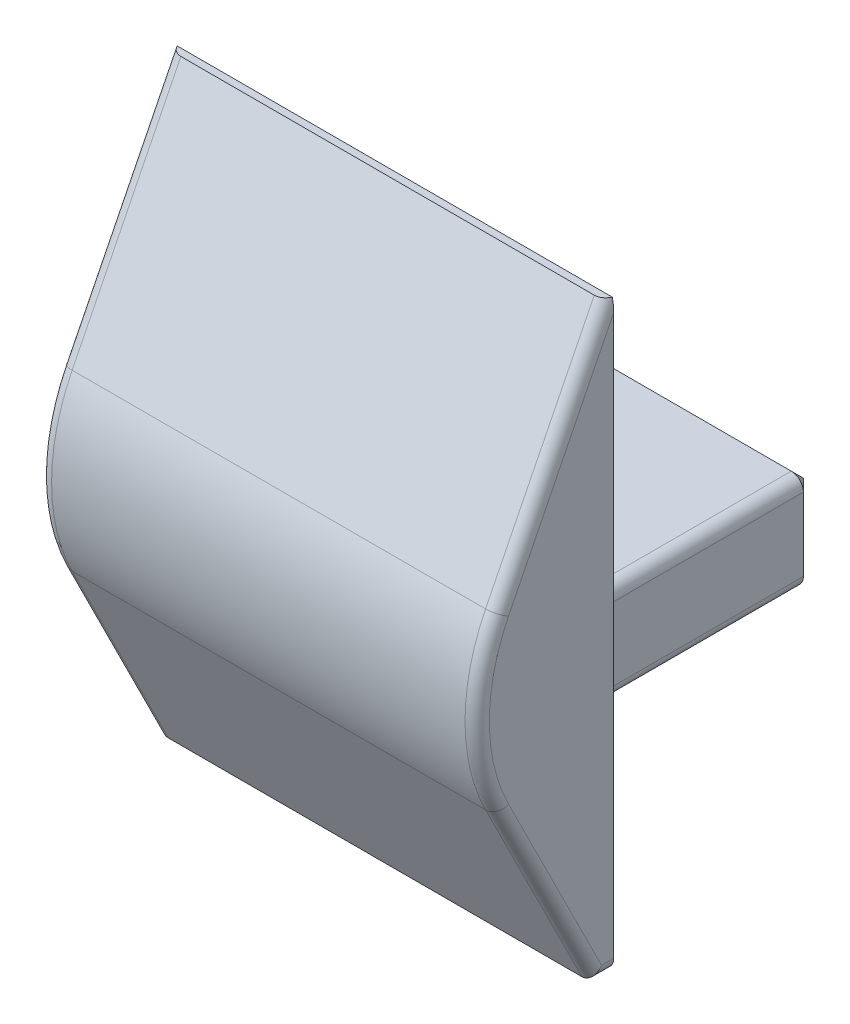
SolidWorks part; units mm, degrees
note: The reader was unsure of these and kept them because the rebuilt part matched: shared geometry of "Sketch3<4>".
ref_plane "Front Plane" through (0, 0, 0) normal (0, 0, 1) x (1, 0, 0)
ref_plane "Top Plane" through (0, 0, 0) normal (0, 1, 0) x (1, 0, 0)
ref_plane "Right Plane" through (0, 0, 0) normal (1, 0, 0) x (0, 0, -1)
ref_plane "Plane1" through (25.9401, 0, 0) normal (1, 0, 0) x (0, 0, -1)
sketch "Sketch3" plane through (25.9401, 0, 0) normal (1, 0, 0) x (0, 0, -1)
  line L0 (-28.7936, -877.6366) -> (-28.7936, -854.6366)
  line L1 (-42.1966, -866.1366) -> (-16.5369, -866.1366) construction
  line L2 (-29.6022, -877.6366) -> (-33.5634, -869.7143)
  line L3 (-29.6022, -854.6366) -> (-33.5634, -862.5589)
  line L4 (-28.7936, -868.1366) -> (-20.2936, -868.1366)
  line L5 (-20.2936, -868.1366) -> (-20.2936, -864.1366)
  line L6 (-28.7936, -864.1366) -> (-20.2936, -864.1366)
  line L7 (-29.6022, -854.6366) -> (-29.0936, -853.6192)
  line L9 (-29.7936, -877.9366) -> (-29.7936, -842.9366) construction
  line L10 (-29.0936, -853.6192) -> (-28.7936, -853.6192)
  line L11 (-28.7936, -854.6366) -> (-28.7936, -853.6192)
  line L14 (-28.7936, -877.6366) -> (-29.6022, -877.6366)
  line L15 (-28.7936, -854.6366) -> (-29.6022, -854.6366)
  line L17 (-26.4602, -877.6366) -> (-28.6936, -877.6366) construction
  line L18 (-29.7936, -877.9366) -> (-34.7936, -867.9366) construction
  line L19 (-20.2936, -678.7366) -> (-20.2936, -853.2366) construction
  arc A0 (-33.5634, -862.5589) -> (-33.5634, -869.7143) centre (-26.408, -866.1366) ccw
  point P9 (-20.2936, -866.1366)
  point P20 (-35.3522, -866.1366)
  dimension "D5" = 8
  dimension "D6" = 0.3
  dimension "D1" = 1
  dimension "D2" = 23
  dimension "D3" = 4
  dimension "D4" = 0.8087
extrude "Boss-Extrude1" add sketch "Sketch3" along normal offset from surface 1 and the other way offset from surface (9 mm away) 1 contours L3 L1 L0 | L1 L2 L0 | L15 L11 L10 L7
extrude "Boss-Extrude2" add sketch "Sketch3<4>" along normal offset from surface 0.1 and the other way offset from surface (8.8 mm away) 0.1 contours L1 L0 L4 L5 | L0 L1 L5 L6
sketch "Sketch3<4>" plane through (25.9401, 0, 0) normal (1, 0, 0) x (0, 0, -1) same geometry as "Sketch3"
fillet "Fillet1" radius 0.5 12 edges at (17.1401, -868.1366, 24.5436) (17.1401, -864.1366, 24.5436) (34.7401, -868.1366, 24.5436) (34.7401, -864.1366, 24.5436) (34.9401, -858.089, 31.3285) (34.9401, -873.6754, 31.5828) (16.9401, -873.6754, 31.5828) (16.9401, -866.1366, 34.408) (34.9401, -866.1366, 34.408) (16.9401, -858.089, 31.3285) (16.9401, -877.6366, 29.1979) (34.9401, -877.6366, 29.1979)
chamfer "Chamfer1" distance 0.5 angle 45 8 edges at (34.7401, -866.1366, 20.2936) (34.5936, -864.283, 20.2936) (34.5936, -867.9901, 20.2936) (25.9401, -864.1366, 20.2936) (25.9401, -868.1366, 20.2936) (17.2865, -864.283, 20.2936) (17.2865, -867.9901, 20.2936) (17.1401, -866.1366, 20.2936)
